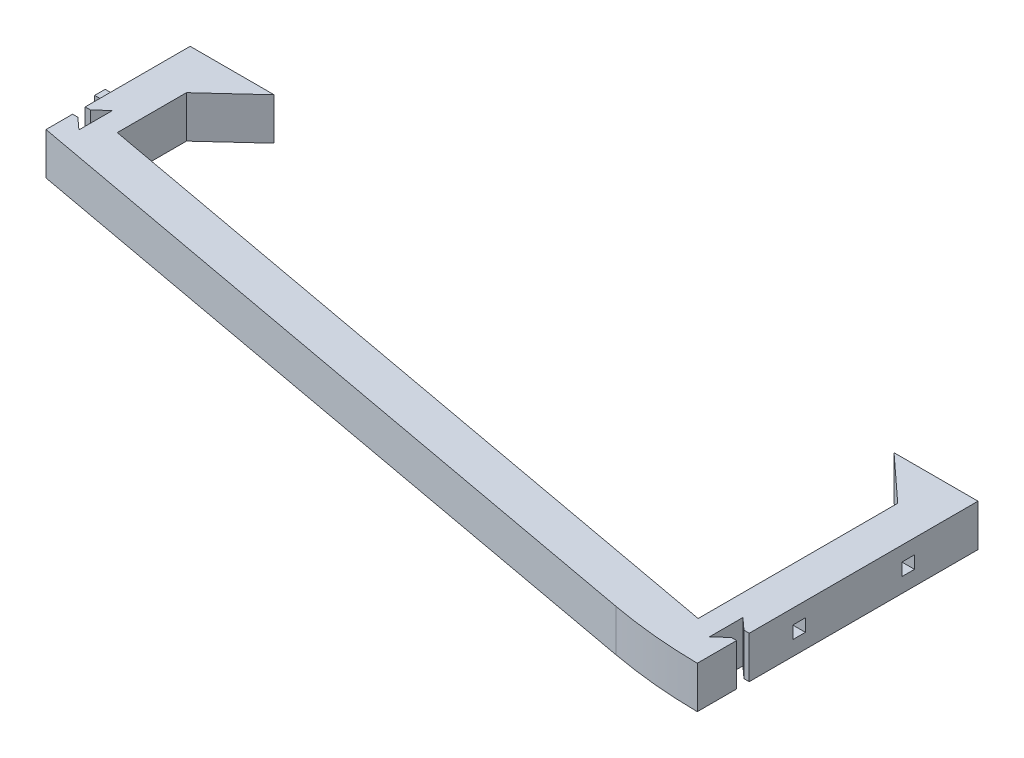
SolidWorks part; units mm, degrees
ref_plane "Přední rovina" through (0, 0, 0) normal (0, 0, 1) x (1, 0, 0)
ref_plane "Horní rovina" through (0, 0, 0) normal (0, 1, 0) x (1, 0, 0)
ref_plane "Pravá rovina" through (0, 0, 0) normal (1, 0, 0) x (0, 0, -1)
sketch "Skica1" plane through (0, 0, 0) normal (0, 1, 0) x (1, 0, 0)
  line L0 (0, 0) -> (0, -55)
  line L1 (0, -55) -> (-150.15, -27.4721)
  line L2 (-150.15, -27.4721) -> (-150.15, 0)
  line L3 (-150.15, 0) -> (-142.85, 0)
  line L4 (-142.85, 0) -> (-142.85, -21.1855)
  line L5 (-142.85, -21.1855) -> (-7.3, -46.0366)
  line L6 (-7.3, -46.0366) -> (-7.3, 0)
  line L7 (-7.3, 0) -> (0, 0)
  dimension "D1" = 55
  dimension "D2" = 7.3
  dimension "D3" = 7.3
  dimension "D4" = 150.15
  dimension "D5" = 7.5
  dimension "D6" = 27.4721
extrude "Přidat vysunutím1" add sketch "Skica1" along normal blind 8
sketch "Skica3" plane through (0, 8, 0) normal (0, 1, 0) x (1, 0, 0)
  line L12 (0, -55) -> (0, 0) construction
  line L13 (-3.2, -41.6) -> (0, -41.6)
  line L14 (-3.2, -41.6) -> (-3.2, -48)
  line L15 (-3.2, -48) -> (0, -48)
  line L16 (0, -41.6) -> (0, -48)
  line L17 (0, -43.6) -> (-1, -43.6)
  line L18 (-1, -43.6) -> (-3.2, -41.6)
  line L19 (-3.2, -48) -> (-1, -46)
  line L20 (-1, -46) -> (0, -46)
  line L21 (0, -46) -> (0, -43.6)
  dimension "D1" = 6.4
  dimension "D2" = 3.2
  dimension "D3" = 2.4
  dimension "D4" = 2
  dimension "D5" = 1
  dimension "D6" = 1
  dimension "D7" = 7
extrude "Odebrat vysunutím1" cut sketch "Skica3" against normal through all contours L19 L20 L16 L17 L18 L14 region at (-1.9157, 8, 44.8)
sketch "Skica6" plane through (0, 8, 0) normal (0, 1, 0) x (1, 0, 0)
  line L9 (-150.15, 0) -> (-134.15, 0)
  line L10 (-150.15, 0) -> (-150.15, -8)
  line L11 (-150.15, -8) -> (-134.15, -8)
  line L12 (-134.15, 0) -> (-134.15, -8)
  line L13 (0, 0) -> (-16, 0)
  line L14 (0, 0) -> (0, -8)
  line L19 (0, -8) -> (-16, -8)
  line L20 (-16, 0) -> (-16, -8)
  dimension "D1" = 8
  dimension "D2" = 16
  dimension "D4" = 8
  dimension "D5" = 16
extrude "Přidat vysunutím3" add sketch "Skica6" against normal blind 8 contours L20 L19 L14 L13 | L9 L12 L11 L10
sketch "Skica9" plane through (0, 0, 0) normal (0, -1, 0) x (1, 0, 0)
  line L8 (-142.85, 8) -> (-134.15, 8)
  line L9 (-134.15, 8) -> (-134.15, 0)
  line L10 (-134.15, 0) -> (-142.85, 8)
  line L11 (-16, 8) -> (-7.3, 8)
  line L12 (-7.3, 8) -> (-16, 0)
  line L13 (-16, 0) -> (-16, 8)
extrude "Odebrat vysunutím4" cut sketch "Skica9" against normal through all
sketch "Skica4" plane through (0, 0, 0) normal (1, 0, 0) x (0, 0, -1)
  line L26 (-35.3, 5.2) -> (-32.9, 5.2)
  line L27 (-35.3, 5.2) -> (-35.3, 2.8)
  line L28 (-35.3, 2.8) -> (-32.9, 2.8)
  line L29 (-32.9, 5.2) -> (-32.9, 2.8)
  line L30 (-14.5, 5.2) -> (-12.1, 5.2)
  line L31 (-14.5, 5.2) -> (-14.5, 2.8)
  line L32 (-14.5, 2.8) -> (-12.1, 2.8)
  line L33 (-12.1, 5.2) -> (-12.1, 2.8)
  line L34 (-43.6, 8) -> (0, 8) construction
  line L35 (-55, 0) -> (-46, 0) construction
  line L37 (0, 8) -> (0, 0) construction
  point P18 (-13.3, 2.8)
  dimension "D4" = 12.1
  dimension "D10" = 2.4
  dimension "D11" = 2.4
  dimension "D12" = 2.8
  dimension "D13" = 2.8
  dimension "D14" = 2.4
  dimension "D15" = 2.4
  dimension "D16" = 18.4
extrude "Odebrat vysunutím2" cut sketch "Skica4" against normal blind 4.4
sketch "Skica5" plane through (-150.15, 0, 0) normal (-1, 0, 0) x (0, 0, 1)
  line L0 (0, 8) -> (27.4721, 8) construction
  line L5 (12.2, 5) -> (14.2, 5)
  line L6 (12.2, 5) -> (12.2, 3)
  line L7 (12.2, 3) -> (14.2, 3)
  line L8 (14.2, 5) -> (14.2, 3)
  line L10 (0, 8) -> (0, 0) construction
  dimension "D1" = 12.2
  dimension "D6" = 2
  dimension "D7" = 2
  dimension "D8" = 3
extrude "Přidat vysunutím2" add sketch "Skica5" along normal blind 4
sketch "Skica10" plane through (0, 8, 0) normal (0, 1, 0) x (1, 0, 0)
  line L0 (-150.15, -22.4) -> (-149.15, -22.4)
  line L5 (-134.15, 0) -> (-150.15, 0) construction
  line L6 (-150.15, 0) -> (-150.15, -27.4721) construction
  line L7 (-150.15, -20) -> (-149.15, -20)
  line L8 (-149.15, -20) -> (-146.95, -18)
  line L9 (-146.95, -18) -> (-146.95, -24.4)
  line L10 (-146.95, -24.4) -> (-149.15, -22.4)
  line L11 (-150.15, -22.4) -> (-150.15, -20)
  dimension "D1" = 6.4
  dimension "D2" = 2.4
  dimension "D3" = 1
  dimension "D4" = 1
  dimension "D5" = 2
  dimension "D6" = 3.2
  dimension "D7" = 18
extrude "Odebrat vysunutím5" cut sketch "Skica10" against normal through all
sketch "Skica11" plane through (0, 8, 0) normal (0, 1, 0) x (1, 0, 0)
  line L0 (0, -53.5) -> (-8.1817, -53.5)
  line L1 (0, -55) -> (0, -46) construction
  line L2 (-150.15, -27.4721) -> (0, -55) construction
  line L3 (-8.1817, -53.5) -> (0, -55)
  line L4 (0, -55) -> (0, -53.5)
  dimension "D1" = 1.5
extrude "Odebrat vysunutím6" cut sketch "Skica11" against normal through all
fillet "Zaoblit1" radius 100 1 edges at (-8.1817, 4, 53.5)
sketch "Skica12" plane through (0, 0, 0) normal (0, 0, -1) x (-1, 0, 0)
  line L0 (0, 0) -> (16, 0) construction
  line L1 (134.15, 0) -> (150.15, 0) construction
  line L2 (150.15, 8) -> (150.15, 0) construction
  line L3 (0, 8) -> (0, 0) construction
  circle A0 centre (3.65, 4) radius 2.2
  circle A1 centre (146.5, 4) radius 2.2
  dimension "D1" = 4.4
  dimension "D2" = 4.4
  dimension "D3" = 4
  dimension "D4" = 4
  dimension "D5" = 3.65
  dimension "D6" = 3.65
extrude "Odebrat vysunutím7" cut sketch "Skica12" against normal blind 2.4
sketch "Skica13" plane through (0, 0, 2.4) normal (0, 0, -1) x (-1, 0, 0)
  circle A0 centre (3.65, 4) radius 1.85
  circle A1 centre (146.5, 4) radius 1.85
  dimension "D1" = 3.7
  dimension "D2" = 3.7
extrude "Odebrat vysunutím8" cut sketch "Skica13" against normal blind 7
